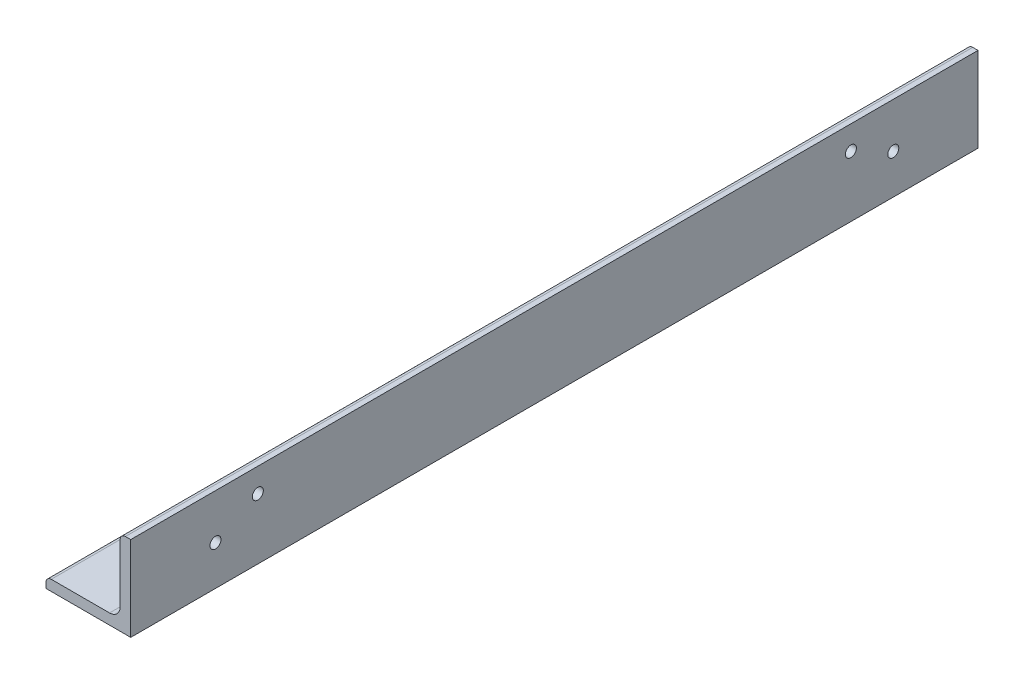
SolidWorks part; units mm, degrees
material "6061-T6 (SS)"
ref_plane "Front Plane" through (0, 0, 0) normal (0, 0, 1) x (1, 0, 0)
ref_plane "Top Plane" through (0, 0, 0) normal (0, 1, 0) x (1, 0, 0)
ref_plane "Right Plane" through (0, 0, 0) normal (1, 0, 0) x (0, 0, -1)
sketch "Sketch0" plane through (0, 0, 0) normal (0, 0, 1) x (1, 0, 0)
  line L0 (-12.7, -12.7) -> (12.7, -12.7)
  line L1 (12.7, -12.7) -> (12.7, 12.7)
  line L2 (12.7, 0) -> (0, 0) construction
  line L3 (0, 0) -> (0, -12.7) construction
  line L4 (9.525, -6.35) -> (9.525, 12.7) construction
  line L5 (6.35, -9.525) -> (-12.7, -9.525) construction
  arc A0 (9.525, -6.35) -> (6.35, -9.525) centre (6.35, -6.35) cw
  point P3 (8.5951, -8.5951)
  dimension "Inside Corner Radius" = 3.175
  dimension "Outside Height" = 25.4
  dimension "Inside Height" = 22.225
  dimension "Inside Width" = 22.225
  dimension "Wall Thickness" = 3.175
  dimension "D1" = 3.175
  dimension "Outside Width" = 25.4
sketch "Sketch1" plane through (0, 0, 0) normal (1, 0, 0) x (0, 0, -1)
  line L0 (127, 0) -> (-127, 0)
  point P4 (0, 0)
  dimension "Length" = 254
sketch "Sketch2" plane through (0, 0, 0) normal (0, 0, 1) x (1, 0, 0)
  line L0 (-12.7, -12.7) -> (12.7, -12.7)
  line L1 (12.7, -12.7) -> (12.7, 12.7)
  line L2 (12.7, 12.7) -> (9.525, 12.7) construction
  line L3 (9.525, 11.1125) -> (9.525, -6.35)
  line L4 (6.35, -9.525) -> (-11.1125, -9.525)
  line L5 (-12.7, -12.7) -> (-12.7, -9.525) construction
  line L6 (11.1125, 12.7) -> (12.7, 12.7)
  line L7 (-12.7, -11.1125) -> (-12.7, -12.7)
  line L8 (12.7, 0) -> (0, 0) construction
  line L9 (0, 0) -> (0, -12.7) construction
  arc A0 (9.525, 11.1125) -> (11.1125, 12.7) centre (11.1125, 11.1125) cw
  arc A1 (-12.7, -11.1125) -> (-11.1125, -9.525) centre (-11.1125, -11.1125) cw
  arc A2 (9.525, -6.35) -> (6.35, -9.525) centre (6.35, -6.35) cw
  dimension "Inside Radius" = 3.175
  dimension "Height" = 25.4
  dimension "Width" = 25.4
  dimension "Thickness" = 3.175
extrude "Boss-Extrude1" add sketch "Sketch2" along normal mid plane 254
sketch "Break Locations" plane through (0, 0, 0) normal (1, 0, 0) x (0, 0, -1)
  line L0 (-101.092, 0) -> (101.092, 0)
  line L1 (-127, -12.7) -> (-127, 12.7) construction
  line L2 (127, -12.7) -> (127, 12.7) construction
  point P0 (-105.41, 0)
  point P1 (105.41, 0)
  point P10 (0, 0)
  point P11 (101.092, 0)
  point P13 (-101.092, 0)
  dimension "D1" = 21.59
  dimension "D2" = 21.59
  dimension "D3" = 25.908
sketch "Sketch4" plane through (0, -9.525, 0) normal (0, 1, 0) x (1, 0, 0)
  line L0 (6.35, 0) -> (-11.1125, 0) construction
  line L1 (6.35, -127) -> (6.35, 127) construction
  line L2 (-11.1125, -127) -> (-11.1125, 127) construction
  line L3 (-2.3812, 127) -> (-2.3812, 101.6) construction
  line L4 (6.35, 127) -> (-11.1125, 127) construction
  line L5 (-2.3812, 101.6) -> (-5.5562, 101.6) construction
  line L6 (0.7938, 88.9079) -> (0.7938, 76.2079) construction
  line L7 (-2.3812, 101.6) -> (0.7938, 101.6) construction
  line L8 (0.7938, 101.6) -> (0.7938, 88.9079) construction
  line L9 (-2.3812, 101.6) -> (-2.3812, 77.7021) construction
  line L12 (-2.3812, 39.4844) -> (-2.3812, 20.5196) construction
  circle A0 centre (-5.5562, 101.6) radius 1.651
  circle A1 centre (0.7938, 88.9079) radius 1.651
  circle A2 centre (0.7938, -88.9079) radius 1.651
  circle A3 centre (-5.5562, -101.6) radius 1.651
  circle A4 centre (-2.3812, 77.7021) radius 6.35
  circle A5 centre (-2.2226, 58.7554) radius 6.3238
  circle A6 centre (-2.0614, 38.6057) radius 6.3238
  circle A7 centre (-2.3837, 20.5515) radius 6.3238
  circle A8 centre (-2.3812, 0) radius 6.4609
  circle A9 centre (-2.0614, -38.6057) radius 6.3238
  circle A10 centre (-2.3837, -20.5515) radius 6.3238
  circle A11 centre (-2.2226, -58.7554) radius 6.3238
  circle A12 centre (-2.3812, -77.7021) radius 6.35
  point P13 (-2.3812, 101.6)
  point P37 (-2.3812, -39.4844)
  dimension "D3" = 3.302
  dimension "D4" = 3.302
  dimension "D8" = 12.7
  dimension "D11" = 12.6476
  dimension "D12" = 12.6476
  dimension "D13" = 12.6476
  dimension "D10" = 18.9467
  dimension "D15" = 20.1498
  dimension "D1" = 25.4
  dimension "D2" = 12.7
  dimension "D5" = 3.175
  dimension "D6" = 12.6921
  dimension "D7" = 3.175
  dimension "D9" = 23.8979
  dimension "D14" = 18.9648
extrude "Cut-Extrude1" cut sketch "Sketch4" against normal through all contours A1 | A0 | A3 | A2 region at (0.7938, -9.525, -88.9079)
sketch "Sketch5" plane through (9.525, 0, 0) normal (-1, 0, 0) x (0, 0, 1)
  line L0 (-127, 2.3812) -> (-101.6, 2.3812) construction
  line L1 (-127, 11.1125) -> (-127, -6.35) construction
  line L2 (-101.6, 2.3812) -> (-101.6, -0.7937) construction
  line L3 (0, 11.1125) -> (0, -6.35) construction
  line L4 (127, 11.1125) -> (-127, 11.1125) construction
  line L5 (127, -6.35) -> (-127, -6.35) construction
  line L6 (-101.6, 2.3812) -> (-101.6, 5.5562) construction
  line L7 (-101.6, 5.5562) -> (-88.9, 5.5562) construction
  circle A0 centre (-88.9, 5.5562) radius 1.651
  circle A1 centre (-101.6, -0.7937) radius 1.651
  circle A2 centre (88.9, 5.5563) radius 1.651
  circle A3 centre (101.6, -0.7937) radius 1.651
  point P7 (-101.6, 2.3812)
  dimension "D3" = 3.302
  dimension "D4" = 3.302
  dimension "D1" = 25.4
  dimension "D2" = 3.175
  dimension "D5" = 3.175
  dimension "D6" = 12.7
extrude "Cut-Extrude2" cut sketch "Sketch5" against normal through all
extrude "Cut-Extrude3" cut sketch "Sketch4<5>" against normal through all
sketch "Sketch4<5>" plane through (0, -9.525, 0) normal (0, 1, 0) x (1, 0, 0) same geometry as "Sketch4"
equation "\"D1@Break Locations\" = .85 * \"Height@Sketch2\""
equation "\"D2@Break Locations\"=\"D1@Break Locations\""
equation "\"Thickness@Sketch2\"=\"wall thickness@sketch0\""
equation "\"Height@Sketch2\"=\"outside height@sketch0\""
equation "\"Width@Sketch2\"=\"outside width@sketch0\""
equation "\"Inside Radius@Sketch2\"=\"inside corner radius@sketch0\""
equation "\"Length@Boss-Extrude1\"=\"length@sketch1\""
equation "\"D3@Break Locations\"=\"D2@Break Locations\"*1.2"
equation "\"D1@Sketch0\"=\"Wall Thickness@Sketch0\""
